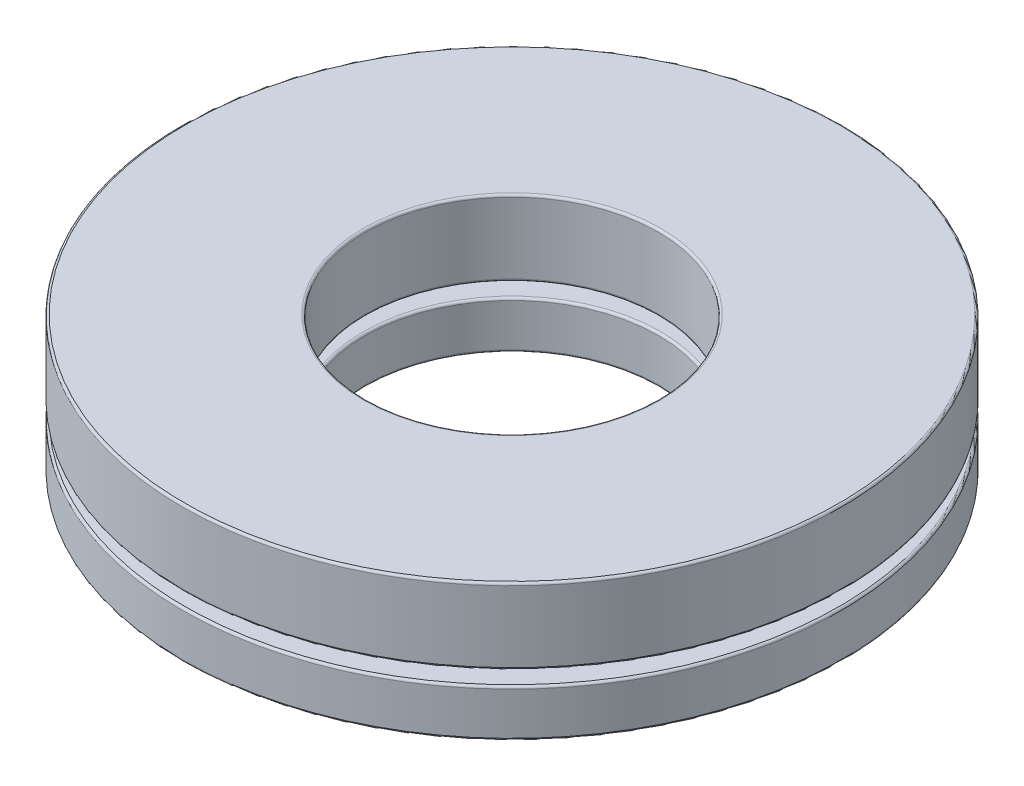
SolidWorks part; units mm, degrees
ref_plane "Front Plane" through (0, 0, 0) normal (0, 0, 1) x (1, 0, 0)
ref_plane "Top Plane" through (0, 0, 0) normal (0, 1, 0) x (1, 0, 0)
ref_plane "Right Plane" through (0, 0, 0) normal (1, 0, 0) x (0, 0, -1)
sketch "Sketch1" plane through (0, 0, 0) normal (1, 0, 0) x (0, 0, -1)
  line L0 (-7.1438, 0) -> (7.1438, 0) construction
  line L1 (0, -2.4511) -> (0, 2.4511) construction
  line L2 (-7.1438, 0.5106) -> (-3.175, 0.5106)
  line L3 (-7.1438, 0.5106) -> (-7.1438, -0.5106)
  line L4 (-7.1438, -0.5106) -> (-3.175, -0.5106)
  line L5 (-3.175, 0.5106) -> (-3.175, -0.5106)
  line L6 (-5.1594, 0.817) -> (-5.1594, -0.817) construction
  circle A0 centre (-5.1594, 0) radius 0.817 construction
  point P13 (-5.1594, 0.5106)
  dimension "OD" = 14.2875
  dimension "Shaft Dia" = 6.35
  dimension "Th" = 4.9022
  dimension "D1" = 1.6341
  dimension "D2" = 1.0213
revolve "Revolve1" add sketch "Sketch1" angle 360 about L1
sketch "Sketch3" plane through (0, 0, 0) normal (1, 0, 0) x (0, 0, -1)
  line L0 (-5.1594, 0.817) -> (-5.1594, -0.817)
  arc A0 (-5.1594, 0.817) -> (-5.1594, -0.817) centre (-5.1594, 0) ccw
  circle A1 centre (-5.1594, 0) radius 0.817 construction
revolve "Cut-Revolve1" cut sketch "Sketch3" angle 360 about L0
sketch "Sketch2" plane through (0, 0, 0) normal (1, 0, 0) x (0, 0, -1)
  line L0 (-5.1594, 0.817) -> (-5.1594, -0.817)
  arc A0 (-5.1594, 0.817) -> (-5.1594, -0.817) centre (-5.1594, 0) ccw
  circle A2 centre (-5.1594, 0) radius 0.817 construction
revolve "Revolve2" add sketch "Sketch2" angle 360 about L0
ref_axis "Axis1" through (0, 2.4511, 0) along (0, -1, 0)
pattern_circular "CirPattern1" count 7 every 51.429 about axis through (0, 2.4511, 0) along (0, -1, 0) of bodies 187
pattern_circular "CirPattern2" count 7 every 51.429 about axis through (0, 2.4511, 0) along (0, -1, 0) of "Cut-Revolve1"
sketch "Sketch4" plane through (0, 0, 0) normal (1, 0, 0) x (0, 0, -1)
  line L0 (-7.1438, 0.5106) -> (-7.1438, -0.5106) construction
  line L1 (-7.1438, 0.817) -> (-3.175, 0.817)
  line L2 (-7.1438, 0.817) -> (-7.1438, 2.4511)
  line L3 (-7.1438, 2.4511) -> (-3.175, 2.4511)
  line L4 (-3.175, 0.817) -> (-3.175, 2.4511)
  line L10 (-3.175, 0.5106) -> (-3.175, -0.5106) construction
  line L11 (0, 0) -> (-7.1438, 0) construction
  line L12 (-7.1438, 0) -> (7.1438, 0) construction
  dimension "D1" = 1.6341
  dimension "D2" = 3.9688
revolve "Revolve3" add sketch "Sketch4" angle 360 about L1
fillet "Fillet1" radius 0.049 4 edges at (0, 0.817, -3.175) (0, 2.4511, -3.175) (0, 0.817, -7.1438) (0, 2.4511, -7.1438)
fillet "Fillet2" radius 0.049 4 edges at (0, -0.5106, -3.175) (0, 0.5106, -3.175) (0, -0.5106, -7.1438) (0, 0.5106, -7.1438)
equation "\"D1@Sketch1\" = \"Th@Sketch1\"/3"
equation "\"D2@Sketch1\" = \"D1@Sketch1\"*.625"
equation "\"Balls@CirPattern1\" = \"OD@Sketch1\"*12"
equation "\"Angle@CirPattern1\" = 360/\"Balls@CirPattern1\""
equation "\"D1@CirPattern2\" = \"Balls@CirPattern1\""
equation "\"D2@CirPattern2\" = \"Angle@CirPattern1\""
equation "\"D1@Fillet1\" = \"Th@Sketch1\"*.01"
equation "\"D1@Fillet2\" = \"D1@Fillet1\""
equation "\"D1@Fillet3\" = \"D1@Fillet1\""
